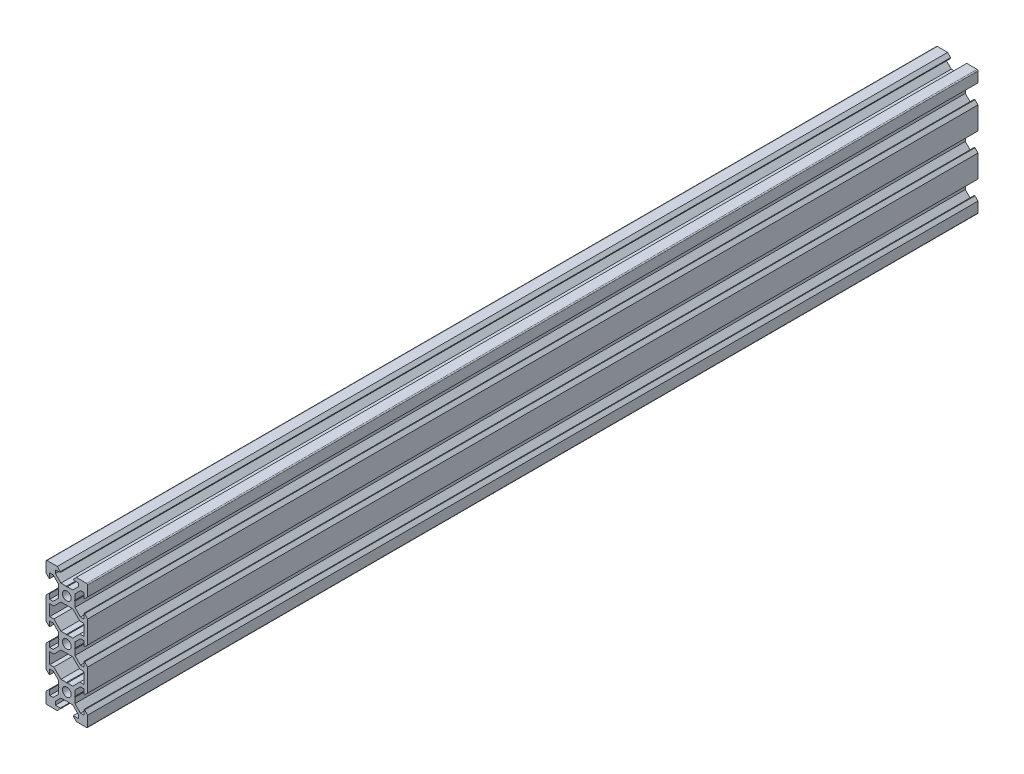
SolidWorks part; units mm, degrees
ref_plane "Plan de face" through (0, 0, 0) normal (0, 0, 1) x (1, 0, 0)
ref_plane "Plan de dessus" through (0, 0, 0) normal (0, 1, 0) x (1, 0, 0)
ref_plane "Plan de droite" through (0, 0, 0) normal (1, 0, 0) x (0, 0, -1)
ref_axis "Axe" through (0, 0, -13.782) along (0, 0, 1)
sketch "Esquisse1" plane through (0, 0, 0) normal (0, 0, 1) x (1, 0, 0)
  line L0 (0, 27.6392) -> (0, -27.6392) construction
  line L1 (-33.6074, 0) -> (33.6074, 0) construction
  line L2 (0, 0) -> (-22.2114, 22.2114) construction
  line L3 (-9.5, 10) -> (-4.58, 10)
  line L4 (-4.58, 10) -> (-3.125, 8.545)
  line L5 (-3.125, 8.545) -> (-3.125, 8.2)
  line L6 (-3.125, 8.2) -> (-5.5, 8.2)
  line L7 (-2.8393, 3.9) -> (-5.5, 6.5607)
  line L8 (-2.8393, 3.9) -> (-0.21, 3.9)
  line L9 (-5.5, 6.5607) -> (-5.5, 8.2)
  line L10 (0, 3.69) -> (0, 2.1)
  line L11 (-3.9, 2.8393) -> (-6.5607, 5.5)
  line L12 (-8.545, 3.125) -> (-8.2, 3.125)
  line L13 (-8.2, 3.125) -> (-8.2, 5.5)
  line L14 (-6.5607, 5.5) -> (-8.2, 5.5)
  line L15 (-10, 4.58) -> (-8.545, 3.125)
  line L16 (-10, 9.5) -> (-10, 4.58)
  line L17 (-0.21, 3.9) -> (0, 3.69)
  line L18 (-3.9, 2.8393) -> (-3.9, 0.21)
  line L19 (-6.2393, -12.7) -> (-8.2, -12.7)
  line L20 (-3.9, 0.21) -> (-3.69, 0)
  line L21 (-0.21, -3.9) -> (0, -3.69)
  line L22 (0, -3.69) -> (0, -2.1)
  line L23 (-6.5607, -5.5) -> (-8.2, -5.5)
  line L24 (-2.8393, -3.9) -> (-0.21, -3.9)
  line L25 (-8.545, -3.125) -> (-8.2, -3.125)
  line L26 (-10, -4.58) -> (-8.545, -3.125)
  line L27 (-8.2, -3.125) -> (-8.2, -5.5)
  line L28 (-2.8393, -3.9) -> (-6.2393, -7.3)
  line L29 (-3.9, -2.8393) -> (-6.5607, -5.5)
  line L30 (-3.9, -2.8393) -> (-3.9, -0.21)
  line L31 (-3.9, -0.21) -> (-3.69, 0)
  line L32 (-6.2393, -7.3) -> (-8.2, -7.3)
  line L33 (-8.2, -7.3) -> (-8.2, -12.7)
  line L34 (-8.2, -10) -> (-10, -10) construction
  line L35 (-10, -15.42) -> (-10, -4.58)
  line L36 (-3.9, -19.79) -> (-3.69, -20)
  line L37 (-3.9, -17.1607) -> (-3.9, -19.79)
  line L38 (-3.9, -17.1607) -> (-6.5607, -14.5)
  line L39 (-2.8393, -16.1) -> (-6.2393, -12.7)
  line L40 (-8.2, -16.875) -> (-8.2, -14.5)
  line L41 (-10, -15.42) -> (-8.545, -16.875)
  line L42 (-8.545, -16.875) -> (-8.2, -16.875)
  line L43 (-2.8393, -16.1) -> (-0.21, -16.1)
  line L44 (-6.5607, -14.5) -> (-8.2, -14.5)
  line L45 (0, -16.31) -> (0, -17.9)
  line L46 (-0.21, -16.1) -> (0, -16.31)
  line L47 (-8.2, -30) -> (-10, -30) construction
  line L48 (-3.69, -20) -> (0, -20) construction
  line L49 (-0.21, -23.9) -> (0, -23.69)
  line L50 (0, -23.69) -> (0, -22.1)
  line L51 (-6.5607, -25.5) -> (-8.2, -25.5)
  line L52 (-2.8393, -23.9) -> (-0.21, -23.9)
  line L53 (-8.545, -23.125) -> (-8.2, -23.125)
  line L54 (-10, -24.58) -> (-8.545, -23.125)
  line L55 (-8.2, -23.125) -> (-8.2, -25.5)
  line L56 (-2.8393, -23.9) -> (-6.2393, -27.3)
  line L57 (-3.9, -22.8393) -> (-6.5607, -25.5)
  line L58 (-3.9, -22.8393) -> (-3.9, -20.21)
  line L59 (-3.9, -20.21) -> (-3.69, -20)
  line L60 (-10, -24.58) -> (-10, -35.42)
  line L61 (-8.2, -32.7) -> (-8.2, -27.3)
  line L62 (-6.2393, -32.7) -> (-8.2, -32.7)
  line L63 (-3.9, -39.79) -> (-3.69, -40)
  line L64 (-3.9, -37.1607) -> (-3.9, -39.79)
  line L65 (-3.9, -37.1607) -> (-6.5607, -34.5)
  line L66 (-2.8393, -36.1) -> (-6.2393, -32.7)
  line L67 (-8.2, -36.875) -> (-8.2, -34.5)
  line L68 (-10, -35.42) -> (-8.545, -36.875)
  line L69 (-8.545, -36.875) -> (-8.2, -36.875)
  line L70 (-2.8393, -36.1) -> (-0.21, -36.1)
  line L71 (-6.5607, -34.5) -> (-8.2, -34.5)
  line L72 (0, -36.31) -> (0, -37.9)
  line L73 (-0.21, -36.1) -> (0, -36.31)
  line L74 (-3.9, -40.21) -> (-3.69, -40)
  line L75 (-6.2393, -27.3) -> (-8.2, -27.3)
  line L76 (-3.9, -42.8393) -> (-3.9, -40.21)
  line L77 (-0.21, -43.9) -> (0, -43.69)
  line L78 (-10, -49.5) -> (-10, -44.58)
  line L79 (-10, -44.58) -> (-8.545, -43.125)
  line L80 (-6.5607, -45.5) -> (-8.2, -45.5)
  line L81 (-8.2, -43.125) -> (-8.2, -45.5)
  line L82 (-8.545, -43.125) -> (-8.2, -43.125)
  line L83 (-3.9, -42.8393) -> (-6.5607, -45.5)
  line L84 (0, -43.69) -> (0, -42.1)
  line L85 (-5.5, -46.5607) -> (-5.5, -48.2)
  line L86 (-2.8393, -43.9) -> (-0.21, -43.9)
  line L87 (-2.8393, -43.9) -> (-5.5, -46.5607)
  line L88 (-3.125, -48.2) -> (-5.5, -48.2)
  line L89 (-3.125, -48.545) -> (-3.125, -48.2)
  line L90 (-4.58, -50) -> (-3.125, -48.545)
  line L91 (-9.5, -50) -> (-4.58, -50)
  arc A0 (0, -2.1) -> (0, 2.1) centre (0, 0) cw
  arc A1 (-9.5, 10) -> (-10, 9.5) centre (-9.5, 9.5) ccw
  arc A2 (0, -37.9) -> (0, -42.1) centre (0, -40) ccw
  arc A3 (-9.5, -50) -> (-10, -49.5) centre (-9.5, -49.5) cw
  arc A4 (0, -17.9) -> (0, -22.1) centre (0, -20) ccw
  point P4 (0, 0)
  point P7 (0, 0)
  point P30 (-10, 10)
  point P60 (0, -20)
  point P111 (-10, -50)
  dimension "D5" = 11
  dimension "D2" = 2.1
  dimension "D3" = 6.25
  dimension "D10" = 0.5
  dimension "D4" = 9.16
  dimension "D6" = 1.5
  dimension "D7" = 1.8
  dimension "D8" = 4.3
  dimension "D9" = 20
  dimension "D11" = 0.42
  dimension "D12" = 10
  dimension "D13" = 1.8
extrude "Boss.-Extru.1" add sketch "Esquisse1" along normal blind 427.7
sketch "Esquisse3" plane through (0, 0, 427.7) normal (0, 0, 1) x (1, 0, 0)
  line L0 (0, 0) -> (-9.8536, 9.8536) construction
  line L1 (-8.2, 8.2) -> (-8.2, 6.57)
  line L2 (-8.2, 6.57) -> (-7.54, 6.57)
  line L3 (-7.54, 6.57) -> (-6.57, 7.54)
  line L4 (-8.2, 3.125) -> (-8.2, 5.5) construction
  line L5 (-6.57, 8.2) -> (-6.57, 7.54)
  line L6 (-8.2, 8.2) -> (-6.57, 8.2)
  line L7 (-5.5, 6.5607) -> (-5.5, 8.2) construction
  line L8 (-3.69, -20) -> (0, -20) construction
  line L9 (-8.2, -48.2) -> (-6.57, -48.2)
  line L10 (-6.57, -48.2) -> (-6.57, -47.54)
  line L11 (-7.54, -46.57) -> (-6.57, -47.54)
  line L12 (-8.2, -46.57) -> (-7.54, -46.57)
  line L13 (-8.2, -48.2) -> (-8.2, -46.57)
  arc A0 (-9.5, 10) -> (-10, 9.5) centre (-9.5, 9.5) ccw construction
  point P13 (-7.055, 7.055)
  point P14 (-6.57, 7.87)
  point P26 (-7.055, -47.055)
  dimension "D1" = 1.07
extrude "Enlèv. mat.-Extru.1" [suppressed] cut sketch "Esquisse3" against normal through all
mirror "Symétrie1" about plane through (0, 3.69, 427.7) normal (-1, 0, 0) of "Enlèv. mat.-Extru.1", "Boss.-Extru.1"
